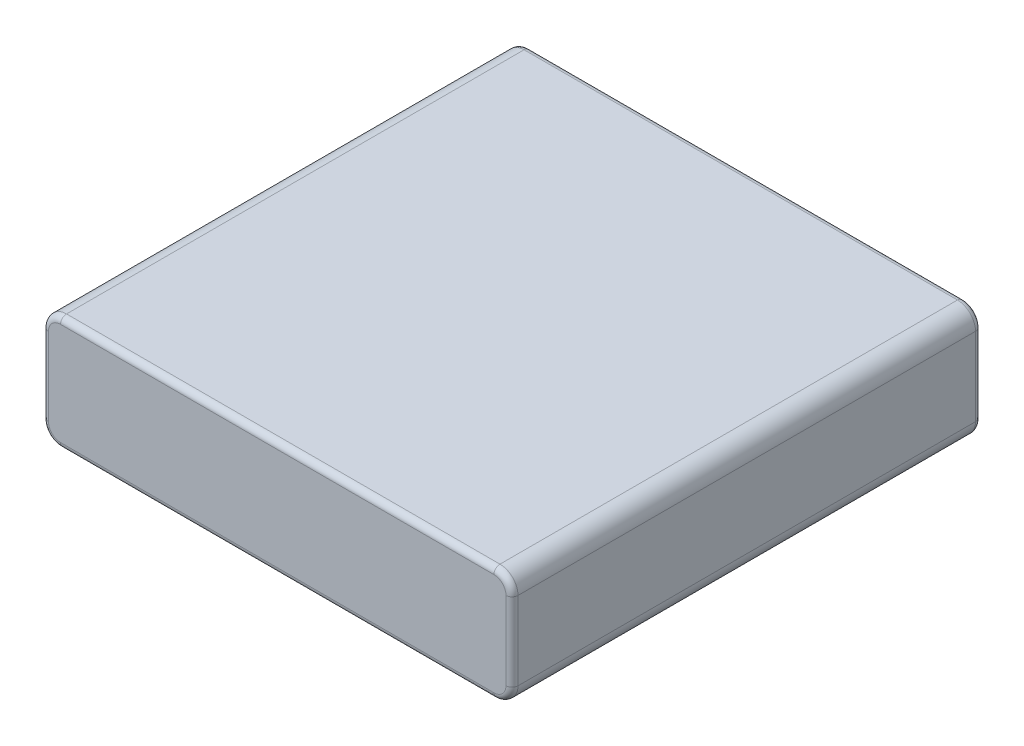
SolidWorks part; units mm, degrees
ref_plane "Front Plane" through (0, 0, 0) normal (0, 0, 1) x (1, 0, 0)
ref_plane "Top Plane" through (0, 0, 0) normal (0, 1, 0) x (1, 0, 0)
ref_plane "Right Plane" through (0, 0, 0) normal (1, 0, 0) x (0, 0, -1)
sketch "Sketch1" plane through (0, 0, 0) normal (0, 1, 0) x (1, 0, 0)
  line L1 (-39, 39) -> (39, 39)
  line L2 (-39, 39) -> (-39, -39)
  line L3 (-39, -39) -> (39, -39)
  line L4 (39, 39) -> (39, -39)
  line L5 (-39, 39) -> (39, -39) construction
  line L6 (-39, -39) -> (39, 39) construction
  point P0 (0, 0)
  dimension "D1" = 78
extrude "Boss-Extrude1" add sketch "Sketch1" along normal mid plane 19
sketch "Sketch2" plane through (0, 0, -39) normal (0, 0, -1) x (-1, 0, 0)
  line L0 (-33, -2.5) -> (-39, -2.5) construction
  line L2 (-39, -9.5) -> (39, -9.5) construction
  circle A0 centre (-33, -2.5) radius 1.75
  dimension "D1" = 3.5
  dimension "D2" = 6
  dimension "D3" = 7
extrude "Cut-Extrude1" cut sketch "Sketch2" against normal blind 19
sketch "Sketch3" plane through (0, -9.5, 0) normal (0, -1, 0) x (1, 0, 0)
  line L0 (39, -39) -> (-39, -39) construction
  line L1 (-24.1, -35) -> (-30.1, -35)
  line L2 (-24.1, -35) -> (-24.1, -31)
  line L3 (-24.1, -31) -> (-30.1, -31)
  line L4 (-30.1, -35) -> (-30.1, -31)
  line L5 (-39, -39) -> (-39, 39) construction
  dimension "D1" = 4
  dimension "D2" = 6
  dimension "D3" = 4
  dimension "D4" = 8.9
extrude "Cut-Extrude2" cut sketch "Sketch3" against normal blind 5
fillet "Fillet2" radius 1 4 edges at (-39, 0, -39) (0, 9.5, -39) (39, 0, -39) (0, -9.5, -39)
fillet "Fillet3" radius 3 8 edges at (-38.7071, 9.2071, -38.7071) (-38.7071, -9.2071, -38.7071) (38.7071, 9.2071, -38.7071) (38.7071, -9.2071, -38.7071) (-39, 9.5, 0.5) (-39, -9.5, 0.5) (39, 9.5, 0.5) (39, -9.5, 0.5)
fillet "Fillet4" radius 1 8 edges at (38.1213, 8.6213, 39) (0, 9.5, 39) (-38.1213, 8.6213, 39) (-39, 0, 39) (-38.1213, -8.6213, 39) (0, -9.5, 39) (38.1213, -8.6213, 39) (39, 0, 39)
